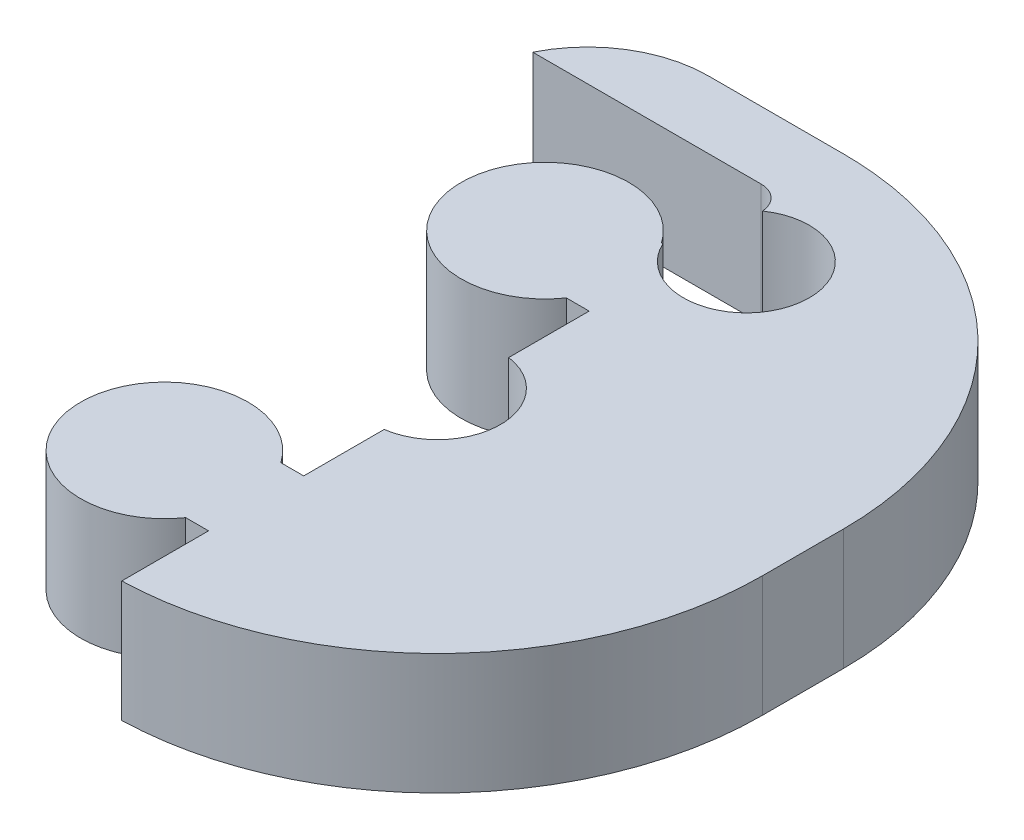
SolidWorks part; units mm, degrees
ref_plane "Front Plane" through (0, 0, 0) normal (0, 0, 1) x (1, 0, 0)
ref_plane "Top Plane" through (0, 0, 0) normal (0, 1, 0) x (1, 0, 0)
ref_plane "Right Plane" through (0, 0, 0) normal (1, 0, 0) x (0, 0, -1)
sketch "Sketch1" plane through (0, 0, 0) normal (0, 1, 0) x (1, 0, 0)
  line L1 (-25.4, 11.43) -> (25.4, 11.43)
  line L2 (-25.4, 11.43) -> (-25.4, -11.43)
  line L3 (-25.4, -11.43) -> (25.4, -11.43)
  line L4 (25.4, 11.43) -> (25.4, -11.43)
  dimension "D1" = 22.86
  dimension "D2" = 50.8
  dimension "D3" = 11.43
  dimension "D4" = 25.4
extrude "Boss-Extrude1" add sketch "Sketch1" along normal blind 3.175
fillet "Fillet1" radius 10.16 2 edges at (-25.4, 1.5875, 11.43) (25.4, 1.5875, 11.43)
sketch "Sketch3" plane through (0, 3.175, 0) normal (0, 1, 0) x (1, 0, 0)
  line L0 (-7.7526, -1.27) -> (18.5521, -1.27) construction
  circle A0 centre (15.24, -1.27) radius 1.9685
  circle A1 centre (16.637, 6.9948) radius 1.9685
  arc A2 (15.24, -11.43) -> (25.4, -1.27) centre (15.24, -1.27) ccw construction
  circle A3 centre (-3.81, -1.27) radius 1.9685
  dimension "D1" = 3.937
  dimension "D2" = 3.937
  dimension "D6" = 3.937
  dimension "D3" = 8.382
  dimension "D4" = 1.397
  dimension "D5" = 19.05
extrude "Cut-Extrude1" cut sketch "Sketch3" against normal through all
fillet "Fillet3" radius 10.16 2 edges at (-25.4, 1.5875, -11.43) (25.4, 1.5875, -11.43)
scale "Scale1" scale about centroid uniform scaling no x scale factor 0.84 y scale factor 1 z scale factor 0.84
sketch "Sketch4" plane through (0, 3.175, 0) normal (0, 1, 0) x (1, 0, 0)
  line L0 (12.9848, -7.3252) -> (12.9848, -9.6096)
  line L1 (-12.8544, -9.6096) -> (12.7488, -9.6096) construction
  line L3 (12.3848, 5.1748) -> (12.9848, 5.1748)
  line L4 (12.7488, 9.5928) -> (-12.8544, 9.5928) construction
  line L5 (12.9848, -7.3252) -> (12.3848, -7.3252)
  line L6 (12.3848, -4.8252) -> (12.9848, -4.8252)
  line L7 (12.3848, 2.6748) -> (12.9848, 2.6748)
  line L8 (12.9848, 5.1748) -> (12.9848, 7.8248)
  line L9 (-21.3888, 1.0584) -> (-21.3888, -1.0752) construction
  line L10 (12.9848, -9.6096) -> (-21.3888, -9.6096)
  line L11 (6.3531, 7.8248) -> (12.9848, 7.8248)
  line L12 (6.3531, 9.5928) -> (-21.3888, 9.5928)
  line L13 (-21.3888, -9.6096) -> (-21.3888, 9.5928)
  line L14 (6.3531, 7.8248) -> (6.3531, 9.5928)
  line L15 (12.9848, -4.8252) -> (12.9848, 2.6748)
  line L16 (21.2832, -1.0752) -> (21.2832, 1.0584) construction
  arc A0 (12.3848, -7.3252) -> (12.3848, -4.8252) centre (10.5744, -6.0752) cw
  arc A1 (12.3848, 2.6748) -> (12.3848, 5.1748) centre (10.5744, 3.9248) cw
  dimension "D1" = 2.2
  dimension "D2" = 2.2
  dimension "D3" = 14.9301
  dimension "D4" = 1.768
extrude "Cut-Extrude2" cut sketch "Sketch4" against normal through all
fillet "Fillet4" radius 3.175 1 edges at (6.3531, 1.5875, -9.5928)
fillet "Fillet5" radius 0.635 1 edges at (12.9848, 1.5875, -7.8248)
equation "\"D4@Sketch1\"=\"D2@Sketch1\"/2"
equation "\"D3@Sketch1\"=\"D1@Sketch1\"/2"
